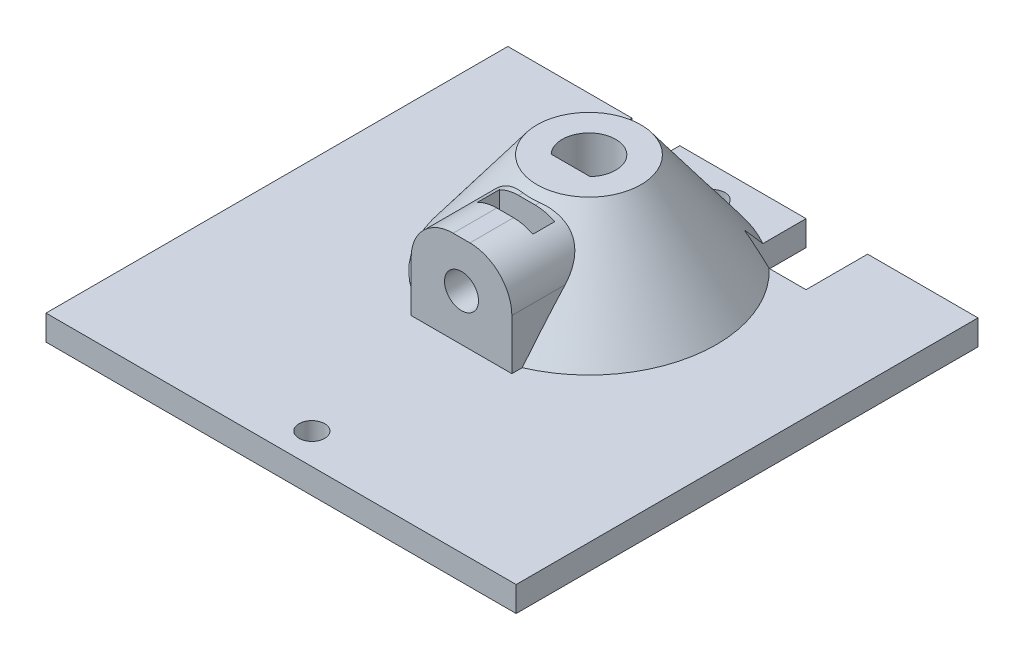
SolidWorks part; units mm, degrees
ref_plane "Front Plane" through (0, 0, 0) normal (0, 0, 1) x (1, 0, 0)
ref_plane "Top Plane" through (0, 0, 0) normal (0, 1, 0) x (1, 0, 0)
ref_plane "Right Plane" through (0, 0, 0) normal (1, 0, 0) x (0, 0, -1)
sketch "Sketch1" plane through (0, 0, 0) normal (0, 1, 0) x (1, 0, 0)
  line L1 (0, 0) -> (56.03, 0)
  line L2 (0, 0) -> (0, 55.04)
  line L3 (0, 55.04) -> (56.03, 55.04)
  line L4 (56.03, 0) -> (56.03, 55.04)
  dimension "D1" = 56.03
  dimension "D2" = 55.04
extrude "Boss-Extrude1" add sketch "Sketch1" along normal blind 3
sketch "Sketch2" plane through (0, 3, 0) normal (0, 1, 0) x (1, 0, 0)
  line L0 (28.015, 55.04) -> (28.015, 36.6932) construction
  line L1 (56.03, 55.04) -> (0, 55.04) construction
  circle A0 centre (28.015, 36.6932) radius 3.19
  circle A1 centre (28.015, 36.6932) radius 6.19
  dimension "D1" = 3
  dimension "D2" = 6.38
extrude "Boss-Extrude2" add sketch "Sketch2" along normal blind 12
ref_plane "Plane1" through (28.015, 0, 0) normal (1, 0, 0) x (0, 0, -1)
sketch "Sketch3" plane through (28.015, 0, 0) normal (1, 0, 0) x (0, 0, -1)
  line L0 (39.8832, 15) -> (42.8832, 15)
  line L1 (42.8832, 15) -> (51.8832, 3)
  line L2 (39.8832, 15) -> (39.8832, 3)
  line L3 (39.8832, 3) -> (51.8832, 3)
  point P4 (39.821, 15)
  dimension "D1" = 12
ref_axis "Axis1" through (28.015, 15, -36.6932) along (0, -1, 0)
revolve "Revolve1" add sketch "Sketch3" angle 360 about axis through (28.015, 15, -36.6932) along (0, -1, 0)
sketch "Sketch4" plane through (0, 15, 0) normal (0, 1, 0) x (1, 0, 0)
  line L0 (28.015, 36.6932) -> (28.015, 25.5032) construction
  line L1 (28.015, 25.5032) -> (38.2873, 25.5032)
  line L2 (38.2873, 25.5032) -> (38.2873, 21.5032)
  line L3 (38.2873, 21.5032) -> (28.015, 21.5032)
  line L4 (28.015, 21.5032) -> (17.7427, 21.5032)
  line L5 (17.7427, 21.5032) -> (17.7427, 25.5032)
  line L6 (17.7427, 25.5032) -> (28.015, 25.5032)
  circle A1 centre (28.015, 36.6932) radius 15.19 construction
  point P3 (0, 0)
  point P11 (0, 0)
  dimension "D1" = 4
extrude "Cut-Extrude1" [suppressed] cut sketch "Sketch4" against normal up to surface (12 mm away)
sketch "Sketch5" plane through (0, 15, 0) normal (0, 1, 0) x (1, 0, 0)
  line L0 (28.015, 33.5032) -> (24.7783, 33.5032)
  line L1 (24.7783, 33.5032) -> (24.7783, 34.5032)
  line L2 (24.7783, 34.5032) -> (31.6982, 34.5032)
  line L3 (31.6982, 34.5032) -> (31.6982, 33.5032)
  line L4 (31.6982, 33.5032) -> (28.015, 33.5032)
  circle A0 centre (28.015, 36.6932) radius 3.19 construction
  circle A1 centre (28.015, 36.6932) radius 3.19 construction
  dimension "D1" = 1
extrude "Boss-Extrude3" add sketch "Sketch5" against normal up to surface (12 mm away) up to face at (28.015, 3, -33.5032)
sketch "Sketch6" [suppressed] plane through (0, 0, -25.5032) normal (0, 0, 1) x (1, 0, 0)
  line L0 (17.7427, 3) -> (38.2873, 3) construction
  line L1 (28.015, 3) -> (28.015, 8.53) construction
  circle A0 centre (28.015, 8.53) radius 2.025
  dimension "D2" = 4.05
  dimension "D1" = 5.53
extrude "Cut-Extrude2" [suppressed] cut sketch "Sketch6" against normal up to surface (9 mm away)
sketch "Sketch7" plane through (28.015, 0, 0) normal (1, 0, 0) x (0, 0, -1)
  line L0 (21.5032, 3) -> (21.5032, 14)
  line L1 (21.5032, 14) -> (34.5032, 14)
  line L3 (34.5032, 15) -> (34.5032, 3) construction
  line L4 (34.5032, 14) -> (34.5032, 3)
  line L5 (34.5032, 3) -> (21.5032, 3)
  dimension "D1" = 11
extrude "Boss-Extrude4" add sketch "Sketch7" along normal blind 6 and the other way blind 6
fillet "Fillet1" radius 5 2 edges at (34.015, 14, -27.3544) (22.015, 14, -27.3544)
sketch "Sketch8" plane through (0, 0, -21.5032) normal (0, 0, 1) x (1, 0, 0)
  line L0 (28.015, 3) -> (28.015, 8.53) construction
  line L1 (0, 3) -> (56.03, 3) construction
  circle A0 centre (28.015, 8.53) radius 2.025
  dimension "D2" = 4.05
  dimension "D1" = 5.53
extrude "Cut-Extrude3" cut sketch "Sketch8" against normal up to surface (13 mm away) up to face at (28.015, 9, -34.5032)
ref_plane "Plane4" through (0, 0, -28.0032) normal (0, 0, 1) x (1, 0, 0)
sketch "Sketch9" plane through (0, 0, -28.0032) normal (0, 0, 1) x (1, 0, 0)
  line L0 (24.715, 10.4353) -> (24.715, 15)
  line L1 (28.015, 4.7195) -> (31.315, 6.6247)
  line L2 (31.315, 6.6247) -> (31.315, 10.4353)
  line L5 (24.715, 10.4353) -> (24.715, 6.6247)
  line L6 (24.715, 6.6247) -> (28.015, 4.7195)
  line L7 (34.205, 15) -> (21.825, 15) construction
  line L8 (31.205, 15) -> (24.825, 15) construction
  line L9 (31.315, 10.4353) -> (31.315, 15)
  line L10 (31.315, 15) -> (24.715, 15)
  line L11 (31.315, 10.4353) -> (29.665, 11.3879) [skipped]
  line L12 (26.365, 11.3879) -> (24.715, 10.4353) [skipped]
  circle A0 centre (28.015, 8.53) radius 3.3 construction
  dimension "D1" = 6.6
extrude "Cut-Extrude4" cut sketch "Sketch9" against normal blind 1.3 and the other way blind 1.3
sketch "Sketch10" plane through (0, 3, 0) normal (0, 1, 0) x (1, 0, 0)
  line L0 (28.015, 55.04) -> (28.015, 51.37) construction
  line L1 (56.03, 55.04) -> (0, 55.04) construction
  line L2 (28.015, 51.37) -> (28.015, 3.67) construction
  line L3 (28.015, 3.67) -> (28.015, 0) construction
  line L4 (0, 0) -> (56.03, 0) construction
  circle A0 centre (28.015, 51.37) radius 1.525
  circle A1 centre (28.015, 3.67) radius 1.525
  dimension "D2" = 3.05
  dimension "D1" = 3.67
extrude "Cut-Extrude5" cut sketch "Sketch10" against normal up to surface (3 mm away) and the other way blind 6 up to face at (28.015, 0, -27.52)
sketch "Sketch11" plane through (0, 3, 0) normal (0, 1, 0) x (1, 0, 0)
  circle A0 centre (28.015, 51.37) radius 3.3091
extrude "Cut-Extrude6" cut sketch "Sketch11" along normal through all
sketch "Sketch12" plane through (0, 0, 0) normal (0, -1, 0) x (1, 0, 0)
  line L0 (56.03, -55.04) -> (0, -55.04) construction
  line L1 (42.8736, -55.04) -> (35.5436, -55.04)
  line L2 (42.8736, -55.04) -> (42.8736, -47.7)
  line L3 (42.8736, -47.7) -> (35.5436, -47.7)
  line L4 (35.5436, -55.04) -> (35.5436, -47.7)
  line L5 (20.49, -51.37) -> (28.015, -51.37) construction
  line L6 (20.49, -55.04) -> (14.81, -55.04)
  line L7 (20.49, -55.04) -> (20.49, -47.7)
  line L8 (20.49, -47.7) -> (14.81, -47.7)
  line L9 (14.81, -55.04) -> (14.81, -47.7)
  line L10 (26.49, -51.37) -> (20.49, -51.37) construction
  line L11 (29.54, -51.37) -> (35.5436, -51.37) construction
  circle A0 centre (28.015, -51.37) radius 1.525 construction
  dimension "D1" = 5.68
  dimension "D2" = 6
  dimension "D3" = 6.0036
  dimension "D4" = 7.33
extrude "Cut-Extrude7" cut sketch "Sketch12" against normal through all
